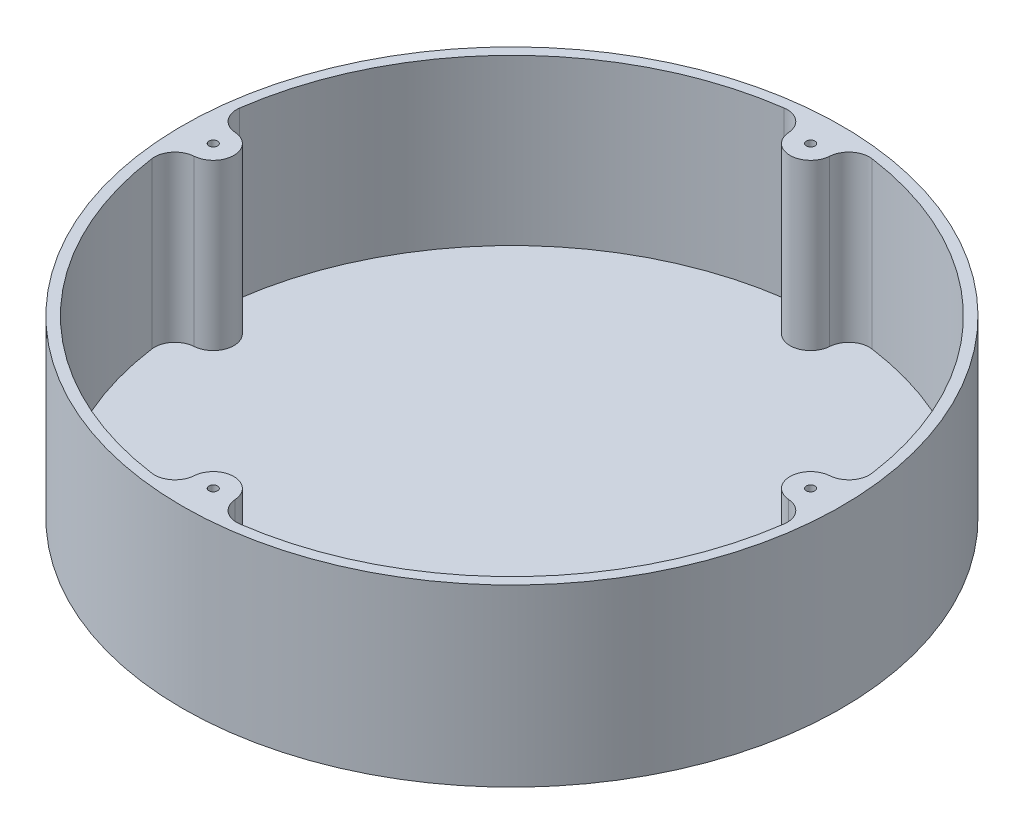
SolidWorks part; units mm, degrees
material "ABS"
ref_plane "Front Plane" through (0, 0, 0) normal (0, 0, 1) x (1, 0, 0)
ref_plane "Top Plane" through (0, 0, 0) normal (0, 1, 0) x (1, 0, 0)
ref_plane "Right Plane" through (0, 0, 0) normal (1, 0, 0) x (0, 0, -1)
sketch "Sketch1" plane through (0, 0, 0) normal (0, 1, 0) x (1, 0, 0)
  circle A0 centre (0, 0) radius 101.6
  dimension "D1" = 203.2
extrude "Boss-Extrude1" add sketch "Sketch1" along normal blind 53.975
sketch "Sketch2" plane through (0, 53.975, 0) normal (0, 1, 0) x (1, 0, 0)
  line L0 (0, 98.425) -> (0, -98.425) construction
  line L1 (-98.425, 0) -> (98.425, 0) construction
  line L2 (-6.35, 92.075) -> (-6.35, 98.2199)
  line L3 (6.3467, 91.8702) -> (6.3467, 98.2202)
  line L4 (92.075, 6.35) -> (98.2199, 6.35)
  line L5 (91.8702, -6.3467) -> (98.2202, -6.3467)
  line L6 (6.35, -92.075) -> (6.35, -98.2199)
  line L7 (-6.3467, -91.8702) -> (-6.3467, -98.2202)
  line L8 (-92.075, -6.35) -> (-98.2199, -6.35)
  line L9 (-91.8702, 6.3467) -> (-98.2202, 6.3467)
  arc A1 (-98.2199, -6.35) -> (-6.3467, -98.2202) centre (0, 0) ccw
  circle A2 centre (0, 0) radius 101.6 construction
  circle A3 centre (0, 92.075) radius 1.3208
  arc A4 (6.3467, 91.8702) -> (-6.35, 92.075) centre (0, 92.075) cw
  arc A5 (91.8702, -6.3467) -> (92.075, 6.35) centre (92.075, 0) cw
  circle A6 centre (92.075, 0) radius 1.3208
  arc A7 (-6.3467, -91.8702) -> (6.35, -92.075) centre (0, -92.075) cw
  circle A8 centre (0, -92.075) radius 1.3208
  arc A9 (-91.8702, 6.3467) -> (-92.075, -6.35) centre (-92.075, 0) cw
  circle A10 centre (-92.075, 0) radius 1.3208
  arc A11 (-6.35, 98.2199) -> (-98.2202, 6.3467) centre (0, 0) ccw
  arc A12 (6.35, -98.2199) -> (98.2202, -6.3467) centre (0, 0) ccw
  arc A13 (98.2199, 6.35) -> (6.3467, 98.2202) centre (0, 0) ccw
  point P36 (0, 0)
  dimension "D1" = 3.175
  dimension "D2" = 2.6416
  dimension "D3" = 6.35
  dimension "D5" = 92.075
  dimension "D6" = 4
  dimension "D4" = 6.35
  dimension "D7" = 92.075
  dimension "D8" = 92.075
  dimension "D9" = 92.075
extrude "Cut-Extrude1" cut sketch "Sketch2" against normal blind 50.8
fillet "Fillet1" radius 6.35 8 edges at (-98.2199, 28.575, 6.35) (-98.2202, 28.575, -6.3467) (-6.35, 28.575, -98.2199) (6.3467, 28.575, -98.2202) (98.2199, 28.575, -6.35) (98.2202, 28.575, 6.3467) (-6.3467, 28.575, 98.2202) (6.35, 28.575, 98.2199)
